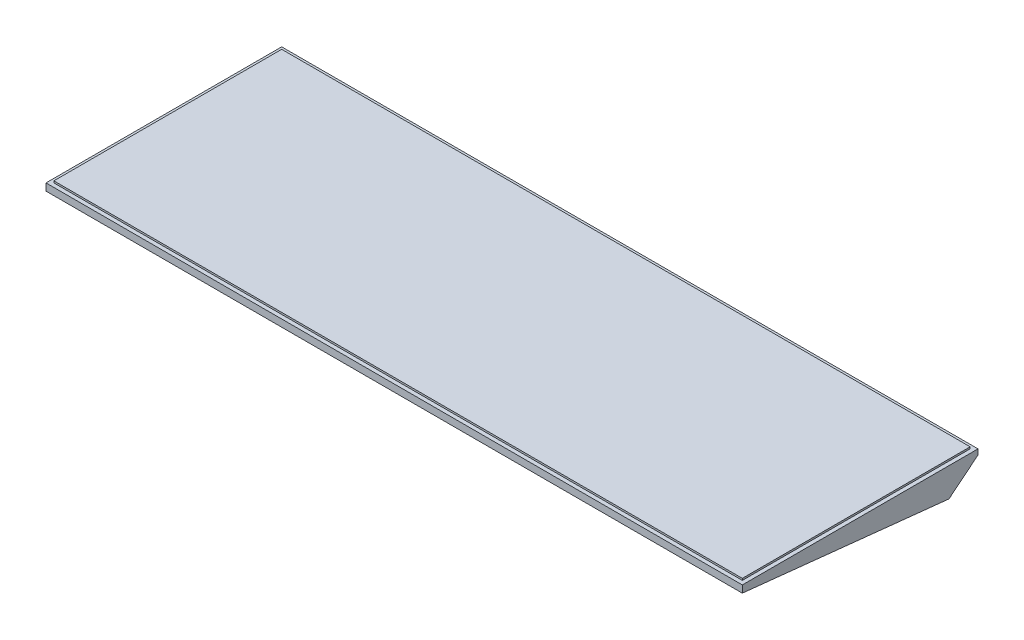
SolidWorks part; units mm, degrees
ref_plane "Front Plane" through (0, 0, 0) normal (0, 0, 1) x (1, 0, 0)
ref_plane "Top Plane" through (0, 0, 0) normal (0, 1, 0) x (1, 0, 0)
ref_plane "Right Plane" through (0, 0, 0) normal (1, 0, 0) x (0, 0, -1)
sketch "Sketch1" plane through (0, 0, 0) normal (0, 1, 0) x (1, 0, 0)
  line L1 (0, 0) -> (390, 0)
  line L2 (0, 0) -> (0, 132)
  line L3 (0, 132) -> (390, 132)
  line L4 (390, 0) -> (390, 132)
  dimension "D1" = 132
  dimension "D2" = 390
extrude "Boss-Extrude1" add sketch "Sketch1" along normal blind 40
sketch "Sketch2" plane through (0, 0, 0) normal (-1, 0, 0) x (0, 0, 1)
  line L0 (0, 36) -> (-115.7425, 23.835)
  line L1 (0, 40) -> (0, 0) construction
  line L2 (-115.7425, 23.835) -> (-132, 37)
  line L3 (-132, 40) -> (-132, 0) construction
  line L4 (-132, 40) -> (0, 40) construction
  point P9 (0, 27.761)
  dimension "D1" = 6
  dimension "D2" = 135
  dimension "D3" = 3
  dimension "D4" = 4
extrude "Cut-Extrude1" cut sketch "Sketch2" against normal through all and the other way through all
sketch "Sketch3" plane through (0, 40, 0) normal (0, 1, 0) x (1, 0, 0)
  line L0 (390, 132) -> (0, 132) construction
  line L1 (387.8, 2.2) -> (2.2, 2.2)
  line L2 (387.8, 2.2) -> (387.8, 129.8)
  line L3 (387.8, 129.8) -> (2.2, 129.8)
  line L4 (2.2, 2.2) -> (2.2, 129.8)
  line L5 (390, 0) -> (390, 132) construction
  line L6 (0, 0) -> (390, 0) construction
  point P4 (195, 129.8)
  point P7 (195, 132)
  point P8 (387.8, 66)
  point P11 (390, 66)
  dimension "D1" = 2.2
  dimension "D2" = 2.2
extrude "Boss-Extrude2" add sketch "Sketch3" along normal blind 1
sketch "Sketch4" plane through (0, 35.6067, -3.7424) normal (0, -0.9945, 0.1045) x (1, 0, 0)
  line L0 (197.9, -58.237) -> (195.9, -58.237) construction
  line L1 (197.9, -66.237) -> (195.9, -66.237)
  line L2 (197.9, -66.237) -> (197.9, -50.237)
  line L3 (197.9, -50.237) -> (195.9, -50.237)
  line L4 (195.9, -66.237) -> (195.9, -50.237)
  line L5 (202.4, -58.737) -> (200.4, -58.737)
  line L6 (202.4, -58.737) -> (202.4, -46.237)
  line L7 (202.4, -46.237) -> (200.4, -46.237)
  line L8 (200.4, -58.737) -> (200.4, -46.237)
  line L9 (193.1, -58.737) -> (191.1, -58.737)
  line L10 (193.1, -58.737) -> (193.1, -50.737)
  line L11 (193.1, -50.737) -> (191.1, -50.737)
  line L12 (191.1, -58.737) -> (191.1, -50.737)
  line L13 (189.6, -58.737) -> (187.6, -58.737)
  line L14 (189.6, -58.737) -> (189.6, -50.737)
  line L15 (189.6, -50.737) -> (187.6, -50.737)
  line L16 (187.6, -58.737) -> (187.6, -50.737)
  line L17 (186.1, -58.737) -> (184.1, -58.737)
  line L18 (186.1, -58.737) -> (186.1, -50.737)
  line L19 (186.1, -50.737) -> (184.1, -50.737)
  line L20 (184.1, -58.737) -> (184.1, -50.737)
  line L21 (202.4, -58.737) -> (187.6, -58.737) construction
  line L22 (193.9, -62.237) -> (197.9, -62.237)
  line L23 (193.9, -60.237) -> (197.9, -60.237)
  line L24 (205.9, -50.737) -> (203.9, -50.737)
  line L25 (205.9, -50.737) -> (205.9, -46.237)
  line L26 (205.9, -46.237) -> (203.9, -46.237)
  line L27 (203.9, -50.737) -> (203.9, -46.237)
  line L28 (205.9, -50.737) -> (184.1, -50.737) construction
  line L29 (0, -112.6171) -> (390, -112.6171) construction
  circle A0 centre (201.4, -61.237) radius 1
  circle A1 centre (193.9, -61.237) radius 1
  circle A2 centre (196.9, -65.237) radius 1
  circle A3 centre (196.9, -51.237) radius 1
  circle A4 centre (201.4, -57.737) radius 1
  circle A5 centre (201.4, -47.237) radius 1
  circle A6 centre (204.9, -49.737) radius 1
  circle A7 centre (204.9, -47.237) radius 1
  circle A8 centre (192.1, -57.737) radius 1
  circle A9 centre (192.1, -51.737) radius 1
  circle A10 centre (188.6, -57.737) radius 1
  circle A11 centre (188.6, -51.737) radius 1
  circle A12 centre (185.1, -57.737) radius 1
  circle A13 centre (185.1, -51.737) radius 1
  point P29 (201.4, -58.737)
  point P38 (196.9, -66.237)
  point P63 (195, -112.6171)
  point P64 (195, -50.737)
  dimension "D10" = 2
  dimension "D12" = 2
  dimension "D1" = 16
  dimension "D2" = 2
  dimension "D3" = 2.5
  dimension "D4" = 2.8
  dimension "D5" = 1.5
  dimension "D6" = 1.5
  dimension "D7" = 8
  dimension "D8" = 0.5
  dimension "D9" = 2.5
  dimension "D11" = 12.5
  dimension "D13" = 0
  dimension "D14" = 1.5
  dimension "D15" = 4.5
  dimension "D16" = 2
  dimension "D17" = 3
  dimension "D18" = 11
  dimension "D19" = 66.3801
extrude "Cut-Extrude2" cut sketch "Sketch4" against normal blind 1 contours A5 L8 A4 L6 | A6 | A7 L27 A6 L25 | A7 | A5 | A4 | A0 | A2 | A2 L2 L22 L4 | L23 L4 L22 L2 | A1 | A1 L22 L4 L23 | A3 L4 L23 L2 | A3 | A9 | A9 L12 A8 L10 | A8 | A11 L16 A10 L14 | A10 | A11 | A13 | A13 L20 A12 L18 | A12 region at (196.9, 28.7875, -68.622) region at (196.9, 28.9842, -66.7509) region at (196.9, 29.2056, -64.6439) region at (195.2722, 29.2056, -64.6439) region at (196.9, 29.7398, -59.5616) region at (193.9, 29.2056, -64.6439) region at (196.9, 30.2509, -54.6987) region at (201.4, 29.5715, -61.1631) region at (201.4, 30.1203, -55.9419) region at (201.4, 30.669, -50.7206) region at (192.1, 29.5715, -61.1631) region at (192.1, 29.8851, -58.1795) region at (192.1, 30.1987, -55.196) region at (188.6, 29.5715, -61.1631) region at (188.6, 29.8851, -58.1795) region at (188.6, 30.1987, -55.196) region at (185.1, 29.5715, -61.1631) region at (185.1, 29.8851, -58.1795) region at (185.1, 30.1987, -55.196) region at (204.9, 30.4077, -53.2069) region at (204.9, 30.5384, -51.9638) region at (204.9, 30.669, -50.7206) region at (201.4, 29.2056, -64.6439)
